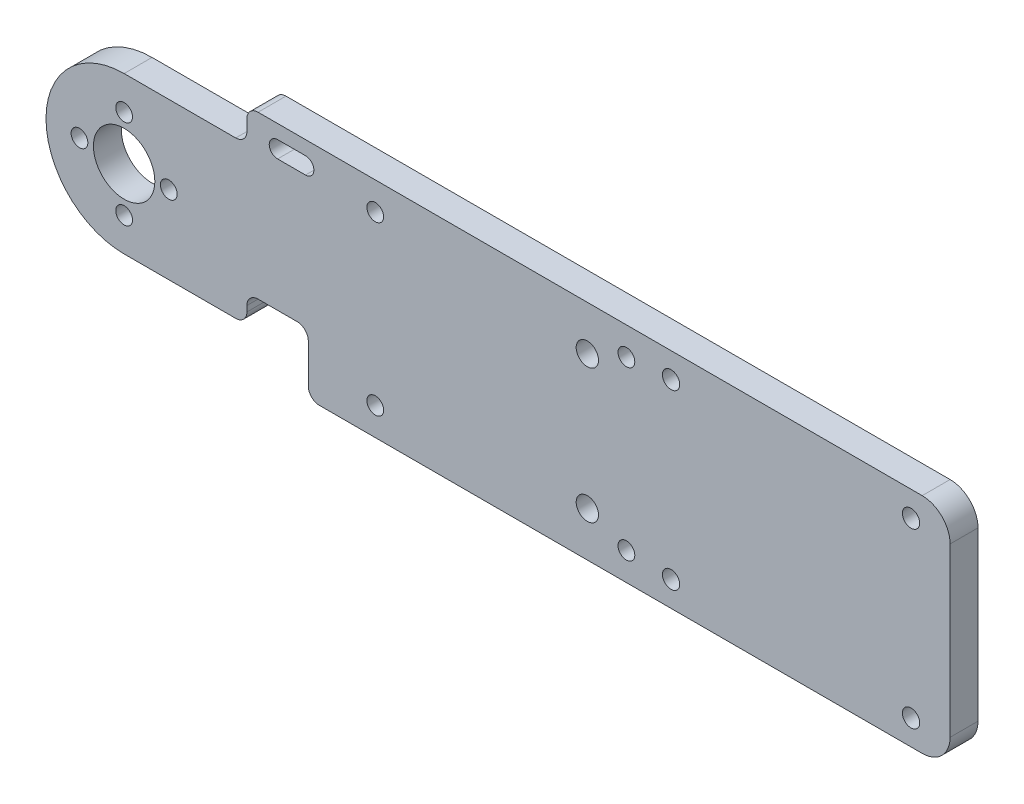
SolidWorks part; units mm, degrees
material "Acrylic (Medium-high impact)"
ref_plane "Front Plane" through (0, 0, 0) normal (0, 0, 1) x (1, 0, 0)
ref_plane "Top Plane" through (0, 0, 0) normal (0, 1, 0) x (1, 0, 0)
ref_plane "Right Plane" through (0, 0, 0) normal (1, 0, 0) x (0, 0, -1)
sketch "Sketch2" plane through (0, 0, 0) normal (0, 0, 1) x (1, 0, 0)
  line L0 (0, 20) -> (0, -20)
  line L1 (0, 20) -> (148, 20)
  line L2 (0, -20) -> (148, -20)
  line L3 (148, 20) -> (148, -20)
  line L4 (0, 0) -> (-17, 0)
  line L5 (0, -14) -> (33, -14)
  line L6 (33, -14) -> (33, -20)
  line L7 (22, 14) -> (22, -14)
  line L8 (0, 14) -> (22, 14)
  line L9 (0, 14) -> (0, 20)
  line L10 (0, 20) -> (22, 20)
  line L11 (22, 14) -> (22, 20)
  line L13 (22, -14) -> (33, -14)
  line L14 (22, -14) -> (22, -9)
  line L15 (22, -9) -> (33, -9)
  line L16 (33, -14) -> (33, -9)
  circle A1 centre (0, 0) radius 5.5
  circle A2 centre (0, 0) radius 14
  dimension "D1" = 148
  dimension "D3" = 11
  dimension "D6" = 28
  dimension "D2" = 165
  dimension "D4" = 40
  dimension "D5" = 20
  dimension "D7" = 33
  dimension "D8" = 22
  dimension "D9" = 5
extrude "Boss-Extrude1" add sketch "Sketch2" along normal mid plane 5 contours A1 L0 A2 | A2 L2 L3 L1 | A1 L4 A2 L0 | A1 L0 A2 L4 | A2 L5 L7 | A2 L7 L8 region at (6.6002, 0, 0) region at (16.0541, 0, 0) region at (-6.6002, 6.6002, 0) region at (86.4144, 0.3567, 0) region at (-6.6002, -6.6002, 0)
fillet "Fillet1" radius 5 2 edges at (148, -20, 0) (148, 20, 0)
sketch "Sketch3" plane through (0, 0, -2.5) normal (0, 0, -1) x (-1, 0, 0)
  line L0 (-119.5, 20) -> (-119.5, -20)
  line L1 (-119.5, 0) -> (-98, 0)
  line L2 (-98, 0) -> (-98, 15.5)
  line L9 (-119.5, 0) -> (-75.2347, 0)
  line L12 (0, 0) -> (0, 12)
  line L13 (0, 0) -> (-83, 0)
  line L14 (-32.5, 16) -> (-27.5, 16) construction
  line L17 (-32.5, 17.5) -> (-27.5, 17.5)
  line L18 (-32.5, 14.5) -> (-27.5, 14.5)
  line L19 (0, 0) -> (18.4819, 0)
  line L21 (-83, 0) -> (-83, 12)
  line L25 (-148, 15) -> (-148, -15)
  line L27 (-148, 15) -> (-148, -15)
  line L29 (-143, -20) -> (-33, -20)
  line L31 (-143, -20) -> (-33, -20)
  line L33 (-22, 20) -> (-143, 20)
  line L35 (-22, 20) -> (-143, 20)
  line L36 (-33, -20) -> (-33, -9)
  line L37 (-33, -20) -> (-33, -9)
  line L38 (-22, -14) -> (0, -14)
  line L39 (-22, -14) -> (0, -14)
  line L40 (0, 14) -> (-22, 14)
  line L41 (0, 14) -> (-22, 14)
  line L42 (-22, 14) -> (-22, 20)
  line L43 (-22, 14) -> (-22, 20)
  line L44 (-33, -9) -> (-22, -9)
  line L45 (-33, -9) -> (-22, -9)
  line L46 (-22, -9) -> (-22, -14)
  line L47 (-22, -9) -> (-22, -14)
  circle A0 centre (0, 0) radius 12
  circle A1 centre (-98, 15.5) radius 1.55
  circle A2 centre (-98, -15.5) radius 1.55
  arc A4 (0, -14) -> (0, 14) centre (0, 0) ccw
  arc A7 (0, -14) -> (0, 14) centre (0, 0) ccw
  circle A9 centre (-141, -15.5) radius 1.55
  circle A10 centre (-141, 15.5) radius 1.55
  circle A12 centre (-90, -15) radius 1.5
  circle A13 centre (-45, -15) radius 1.5
  arc A21 (-32.5, 17.5) -> (-32.5, 14.5) centre (-32.5, 16) ccw
  arc A22 (-27.5, 14.5) -> (-27.5, 17.5) centre (-27.5, 16) ccw
  circle A23 centre (-83, 12) radius 2
  circle A24 centre (-90, 15) radius 1.5
  circle A25 centre (-83, -12) radius 2
  circle A26 centre (-45, 15) radius 1.5
  circle A27 centre (0, 0) radius 8
  circle A28 centre (0, -8) radius 1.5
  circle A29 centre (-8, 0) radius 1.5
  circle A30 centre (0, 8) radius 1.5
  circle A31 centre (8, 0) radius 1.5
  arc A33 (-148, -15) -> (-143, -20) centre (-143, -15) ccw
  arc A34 (-148, -15) -> (-143, -20) centre (-143, -15) ccw
  arc A35 (-143, 20) -> (-148, 15) centre (-143, 15) ccw
  arc A36 (-143, 20) -> (-148, 15) centre (-143, 15) ccw
  point P8 (-20.5, 12)
  point P22 (0, 0)
  point P35 (-30, 16)
  point P48 (12, 0)
  point P53 (-12, 0)
  point P54 (-7.6279, -12)
  dimension "D6" = 3.1
  dimension "D10" = 15
  dimension "D11" = 16
  dimension "D13" = 45
  dimension "D17" = 3
  dimension "D18" = 4
  dimension "D12" = 3
  dimension "D19" = 16
  dimension "D21" = 4
  dimension "D22" = 3
  dimension "D3" = 21.5
  dimension "D4" = 15.5
  dimension "D5" = 98
  dimension "D7" = 7
  dimension "D8" = 15
  dimension "D9" = 30
  dimension "D14" = 5
  dimension "D15" = 3
  dimension "D16" = 16
  dimension "D20" = 12
  dimension "D1" = 0
extrude "Cut-Extrude1" cut sketch "Sketch3" against normal through all contours L18 A22 L17 A21 | A23 L21 | L21 A23 | A25 | A12 | A2 | A1 | A10 | A9 | A27 A28 | A27 A28 | L19 A31 A27 | A27 A31 L19 | L19 A31 A27 | A27 A31 L19 | A27 A29 L13 | L13 A29 A27 | A27 A29 L13 | L13 A29 A27 | A27 A30 L12 | L12 A30 A27 | A27 A30 L12 | L12 A30 A27 region at (99.065, 16.565, -2.5) region at (84.3742, 13.3742, -2.5) region at (8.6106, 0.6553, -2.5) region at (8.6106, -0.6553, -2.5) region at (-8.6106, -0.6553, -2.5) region at (-8.6106, 0.6553, -2.5) region at (7.3387, 0.6164, -2.5) region at (7.3387, -0.6164, -2.5) region at (-0.6553, 8.6106, -2.5) region at (0.6553, 8.6106, -2.5) region at (-7.3387, -0.6164, -2.5) region at (-7.3387, 0.6164, -2.5) region at (0.6164, 7.3387, -2.5) region at (0, -7.3387, -2.5) region at (0, -8.6106, -2.5) region at (-0.6164, 7.3387, -2.5) region at (30, 16, -2.5) region at (98, -15.5, -2.5) region at (141, -15.5, -2.5) region at (141, 15.5, -2.5) region at (90, -15, -2.5) region at (83, -12, -2.5)
extrude "Cut-Extrude2" cut sketch "Sketch3<4>" against normal blind 10 contours L18 A22 L17 A21 | A12 | A13 | A10 | A9 | A1 | A2 | L21 A23 | A23 L21 | A25 | A26 | A24 region at (99.065, 16.565, -2.5) region at (84.3742, 13.3742, -2.5) region at (30, 16, -2.5) region at (98, -15.5, -2.5) region at (141, -15.5, -2.5) region at (141, 15.5, -2.5) region at (90, -15, -2.5) region at (45, -15, -2.5) region at (90, 15, -2.5) region at (83, -12, -2.5) region at (45, 15, -2.5)
sketch "Sketch3<4>" plane through (0, 0, -2.5) normal (0, 0, -1) x (-1, 0, 0) same geometry as "Sketch3"
fillet "Fillet2" radius 2 6 edges at (33, -20, 0) (22, 20, 0) (22, 14, 0) (33, -9, 0) (22, -14, 0) (22, -9, 0)
